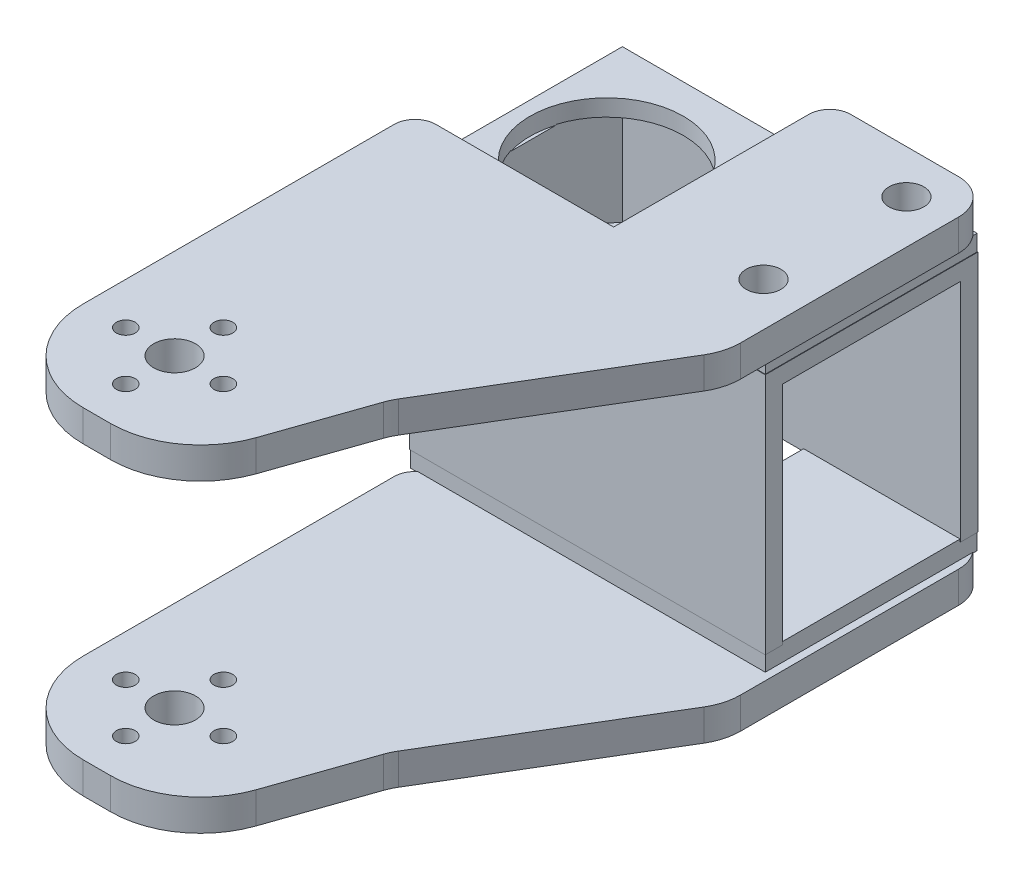
SolidWorks part; units mm, degrees
ref_plane "Front Plane" through (0, 0, 0) normal (0, 0, 1) x (1, 0, 0)
ref_plane "Top Plane" through (0, 0, 0) normal (0, 1, 0) x (1, 0, 0)
ref_plane "Right Plane" through (0, 0, 0) normal (1, 0, 0) x (0, 0, -1)
ref_plane "PY_m23_125" through (0, -23.125, 0) normal (0, 1, 0) x (1, 0, 0)
sketch "S_prism1" plane through (0, -23.125, 0) normal (0, 1, 0) x (1, 0, 0)
  line L0 (-0.1, -13) -> (3.8289, -13)
  line L1 (16.0129, -4.3379) -> (20.7288, 9.2202)
  line L2 (21.4248, 10.708) -> (37.8599, 38.0999)
  line L3 (39, 42.2159) -> (39, 73.5)
  line L4 (34, 78.5) -> (18.5, 78.5)
  line L5 (15.5, 75.5) -> (15.5, 47.5)
  line L6 (15.5, 47.5) -> (-10, 47.5)
  line L7 (-13, 44.5) -> (-13, -0.1)
  arc A0 (-13, -0.1) -> (-0.1, -13) centre (-0.1001, -0.1001) ccw
  arc A1 (3.8289, -13) -> (16.0129, -4.3379) centre (3.8289, -0.1) ccw
  arc A2 (20.7288, 9.2202) -> (21.4248, 10.708) centre (28.2833, 6.5929) cw
  arc A3 (37.8599, 38.0999) -> (39, 42.2159) centre (31, 42.2159) ccw
  arc A4 (39, 73.5) -> (34, 78.5) centre (33.9999, 73.4999) ccw
  arc A5 (18.5, 78.5) -> (15.5, 75.5) centre (18.5001, 75.4999) ccw
  arc A6 (-10, 47.5) -> (-13, 44.5) centre (-9.9999, 44.4999) ccw
extrude "Boss_1" add sketch "S_prism1" along normal blind 4.5
ref_plane "PY_p18_625" through (0, 18.625, 0) normal (0, 1, 0) x (1, 0, 0)
sketch "S_cyl2" plane through (0, 18.625, 0) normal (0, 1, 0) x (1, 0, 0)
  circle A0 centre (0, 0) radius 9
  dimension "D1_S_cyl2" = 18
extrude "Boss_2" add sketch "S_cyl2" along normal blind 2
ref_plane "PY_p20_625" through (0, 20.625, 0) normal (0, 1, 0) x (1, 0, 0)
sketch "S_prism3" plane through (0, 20.625, 0) normal (0, 1, 0) x (1, 0, 0)
  line L0 (-0.1, -13) -> (3.8289, -13)
  line L1 (16.0129, -4.3379) -> (20.7288, 9.2202)
  line L2 (21.4248, 10.708) -> (37.8599, 38.0999)
  line L3 (39, 42.2159) -> (39, 73.5)
  line L4 (34, 78.5) -> (18.5, 78.5)
  line L5 (15.5, 75.5) -> (15.5, 47.5)
  line L6 (15.5, 47.5) -> (-10, 47.5)
  line L7 (-13, 44.5) -> (-13, -0.1)
  arc A0 (-13, -0.1) -> (-0.1, -13) centre (-0.1001, -0.1001) ccw
  arc A1 (3.8289, -13) -> (16.0129, -4.3379) centre (3.8289, -0.1) ccw
  arc A2 (20.7288, 9.2202) -> (21.4248, 10.708) centre (28.2833, 6.5929) cw
  arc A3 (37.8599, 38.0999) -> (39, 42.2159) centre (31, 42.2159) ccw
  arc A4 (39, 73.5) -> (34, 78.5) centre (33.9999, 73.4999) ccw
  arc A5 (18.5, 78.5) -> (15.5, 75.5) centre (18.5001, 75.4999) ccw
  arc A6 (-10, 47.5) -> (-13, 44.5) centre (-9.9999, 44.4999) ccw
extrude "Boss_3" add sketch "S_prism3" along normal blind 4.5
ref_plane "PZ_m77_260" through (0, 0, -77.26) normal (0, 0, 1) x (1, 0, 0)
sketch "S_box4" plane through (0, 0, -77.26) normal (0, 0, 1) x (1, 0, 0)
  line L0 (-13.01, -16.4) -> (-10.51, -16.4)
  line L1 (-10.51, -16.4) -> (-10.51, 18.4)
  line L2 (-10.51, 18.4) -> (-13.01, 18.4)
  line L3 (-13.01, 18.4) -> (-13.01, -16.4)
  dimension "P1" = 13.01
  dimension "P2" = 16.4
  dimension "P3" = 10.51
  dimension "P4" = 16.4
  dimension "P5" = 10.51
  dimension "P6" = 18.4
  dimension "P7" = 13.01
  dimension "P8" = 18.4
extrude "Boss_4" add sketch "S_box4" along normal blind 30.52
sketch "S_box5" plane through (0, 0, -77.26) normal (0, 0, 1) x (1, 0, 0)
  line L0 (-13.01, -16.4) -> (38.01, -16.4)
  line L1 (38.01, -16.4) -> (38.01, 18.4)
  line L2 (38.01, 18.4) -> (-13.01, 18.4)
  line L3 (-13.01, 18.4) -> (-13.01, -16.4)
  dimension "P1" = 13.01
  dimension "P2" = 16.4
  dimension "P3" = 38.01
  dimension "P4" = 16.4
  dimension "P5" = 38.01
  dimension "P6" = 18.4
  dimension "P7" = 13.01
  dimension "P8" = 18.4
extrude "Boss_5" add sketch "S_box5" along normal blind 2.5
ref_plane "PZ_m49_240" through (0, 0, -49.24) normal (0, 0, 1) x (1, 0, 0)
sketch "S_box6" plane through (0, 0, -49.24) normal (0, 0, 1) x (1, 0, 0)
  line L0 (-13.01, -16.4) -> (38.01, -16.4)
  line L1 (38.01, -16.4) -> (38.01, 18.4)
  line L2 (38.01, 18.4) -> (-13.01, 18.4)
  line L3 (-13.01, 18.4) -> (-13.01, -16.4)
  dimension "P1" = 13.01
  dimension "P2" = 16.4
  dimension "P3" = 38.01
  dimension "P4" = 16.4
  dimension "P5" = 38.01
  dimension "P6" = 18.4
  dimension "P7" = 13.01
  dimension "P8" = 18.4
extrude "Boss_6" add sketch "S_box6" along normal blind 2.5
sketch "S_box7" plane through (0, 0, -77.26) normal (0, 0, 1) x (1, 0, 0)
  line L0 (-13.01, 16) -> (38.01, 16)
  line L1 (38.01, 16) -> (38.01, 18.4)
  line L2 (38.01, 18.4) -> (-13.01, 18.4)
  line L3 (-13.01, 18.4) -> (-13.01, 16)
  dimension "P1" = 13.01
  dimension "P2" = 16
  dimension "P3" = 38.01
  dimension "P4" = 16
  dimension "P5" = 38.01
  dimension "P6" = 18.4
  dimension "P7" = 13.01
  dimension "P8" = 18.4
extrude "Boss_7" add sketch "S_box7" along normal blind 30.52
ref_plane "PZ_m77_190" through (0, 0, -77.19) normal (0, 0, 1) x (1, 0, 0)
sketch "S_box8" plane through (0, 0, -77.19) normal (0, 0, 1) x (1, 0, 0)
  line L0 (15.5, -18.725) -> (37.94, -18.725)
  line L1 (37.94, -18.725) -> (37.94, -16.05)
  line L2 (37.94, -16.05) -> (15.5, -16.05)
  line L3 (15.5, -16.05) -> (15.5, -18.725)
  dimension "P1" = 15.5
  dimension "P2" = 18.725
  dimension "P3" = 37.94
  dimension "P4" = 18.725
  dimension "P5" = 37.94
  dimension "P6" = 16.05
  dimension "P7" = 15.5
  dimension "P8" = 16.05
extrude "Boss_8" add sketch "S_box8" along normal blind 30.38
ref_plane "PZ_m48_500" through (0, 0, -48.5) normal (0, 0, 1) x (1, 0, 0)
sketch "S_box9" plane through (0, 0, -48.5) normal (0, 0, 1) x (1, 0, 0)
  line L0 (-12.94, -18.725) -> (15.53, -18.725)
  line L1 (15.53, -18.725) -> (15.53, -16.05)
  line L2 (15.53, -16.05) -> (-12.94, -16.05)
  line L3 (-12.94, -16.05) -> (-12.94, -18.725)
  dimension "P1" = 12.94
  dimension "P2" = 18.725
  dimension "P3" = 15.53
  dimension "P4" = 18.725
  dimension "P5" = 15.53
  dimension "P6" = 16.05
  dimension "P7" = 12.94
  dimension "P8" = 16.05
extrude "Boss_9" add sketch "S_box9" along normal blind 1.69
sketch "S_box10" plane through (0, 0, -77.19) normal (0, 0, 1) x (1, 0, 0)
  line L0 (15.5, 18.3) -> (37.94, 18.3)
  line L1 (37.94, 18.3) -> (37.94, 20.725)
  line L2 (37.94, 20.725) -> (15.5, 20.725)
  line L3 (15.5, 20.725) -> (15.5, 18.3)
  dimension "P1" = 15.5
  dimension "P2" = 18.3
  dimension "P3" = 37.94
  dimension "P4" = 18.3
  dimension "P5" = 37.94
  dimension "P6" = 20.725
  dimension "P7" = 15.5
  dimension "P8" = 20.725
extrude "Boss_10" add sketch "S_box10" along normal blind 30.38
sketch "S_box11" plane through (0, 0, -48.5) normal (0, 0, 1) x (1, 0, 0)
  line L0 (-12.94, 18.3) -> (15.53, 18.3)
  line L1 (15.53, 18.3) -> (15.53, 20.725)
  line L2 (15.53, 20.725) -> (-12.94, 20.725)
  line L3 (-12.94, 20.725) -> (-12.94, 18.3)
  dimension "P1" = 12.94
  dimension "P2" = 18.3
  dimension "P3" = 15.53
  dimension "P4" = 18.3
  dimension "P5" = 15.53
  dimension "P6" = 20.725
  dimension "P7" = 12.94
  dimension "P8" = 20.725
extrude "Boss_11" add sketch "S_box11" along normal blind 1.69
ref_plane "PY_m23_225" through (0, -23.225, 0) normal (0, 1, 0) x (1, 0, 0)
sketch "S_hole12" plane through (0, -23.225, 0) normal (0, 1, 0) x (1, 0, 0)
  circle A0 centre (0, 0) radius 3
  dimension "D1_S_hole12" = 6
extrude "Hole_12" cut sketch "S_hole12" along normal blind 4.7
sketch "S_hole13" plane through (0, -23.225, 0) normal (0, 1, 0) x (1, 0, 0)
  circle A0 centre (7, 0) radius 1.35
  dimension "D1_S_hole13" = 2.7
  dimension "P2" = 7
extrude "Hole_13" cut sketch "S_hole13" along normal blind 4.7
sketch "S_hole14" plane through (0, -23.225, 0) normal (0, 1, 0) x (1, 0, 0)
  circle A0 centre (0, -7) radius 1.35
  dimension "D1_S_hole14" = 2.7
  dimension "P2" = 7
extrude "Hole_14" cut sketch "S_hole14" along normal blind 4.7
sketch "S_hole15" plane through (0, -23.225, 0) normal (0, 1, 0) x (1, 0, 0)
  circle A0 centre (-7, 0) radius 1.35
  dimension "D1_S_hole15" = 2.7
  dimension "P2" = 7
extrude "Hole_15" cut sketch "S_hole15" along normal blind 4.7
sketch "S_hole16" plane through (0, -23.225, 0) normal (0, 1, 0) x (1, 0, 0)
  circle A0 centre (0, 7) radius 1.35
  dimension "D1_S_hole16" = 2.7
  dimension "P2" = 7
extrude "Hole_16" cut sketch "S_hole16" along normal blind 4.7
ref_plane "PY_p18_525" through (0, 18.525, 0) normal (0, 1, 0) x (1, 0, 0)
sketch "S_hole17" plane through (0, 18.525, 0) normal (0, 1, 0) x (1, 0, 0)
  circle A0 centre (0, 0) radius 3
  dimension "D1_S_hole17" = 6
extrude "Hole_17" cut sketch "S_hole17" along normal blind 6.7
sketch "S_hole18" plane through (0, 18.525, 0) normal (0, 1, 0) x (1, 0, 0)
  circle A0 centre (7, 0) radius 1.35
  dimension "D1_S_hole18" = 2.7
  dimension "P2" = 7
extrude "Hole_18" cut sketch "S_hole18" along normal blind 6.7
sketch "S_hole19" plane through (0, 18.525, 0) normal (0, 1, 0) x (1, 0, 0)
  circle A0 centre (0, -7) radius 1.35
  dimension "D1_S_hole19" = 2.7
  dimension "P2" = 7
extrude "Hole_19" cut sketch "S_hole19" along normal blind 6.7
sketch "S_hole20" plane through (0, 18.525, 0) normal (0, 1, 0) x (1, 0, 0)
  circle A0 centre (-7, 0) radius 1.35
  dimension "D1_S_hole20" = 2.7
  dimension "P2" = 7
extrude "Hole_20" cut sketch "S_hole20" along normal blind 6.7
sketch "S_hole21" plane through (0, 18.525, 0) normal (0, 1, 0) x (1, 0, 0)
  circle A0 centre (0, 7) radius 1.35
  dimension "D1_S_hole21" = 2.7
  dimension "P2" = 7
extrude "Hole_21" cut sketch "S_hole21" along normal blind 6.7
ref_plane "PY_p15_900" through (0, 15.9, 0) normal (0, 1, 0) x (1, 0, 0)
sketch "S_hole22" plane through (0, 15.9, 0) normal (0, 1, 0) x (1, 0, 0)
  circle A0 centre (0, 62) radius 11
  dimension "D1_S_hole22" = 22
  dimension "P2" = 62
extrude "Hole_22" cut sketch "S_hole22" along normal blind 2.6
sketch "S_hole23" plane through (0, 15.9, 0) normal (0, 1, 0) x (1, 0, 0)
  circle A0 centre (8.3, 51.75) radius 1.1
  dimension "D1_S_hole23" = 2.2
  dimension "P2" = 8.3
  dimension "P3" = 51.75
extrude "Hole_23" cut sketch "S_hole23" along normal blind 2.6
sketch "S_hole24" plane through (0, 15.9, 0) normal (0, 1, 0) x (1, 0, 0)
  circle A0 centre (32.75, 72.25) radius 1.1
  dimension "D1_S_hole24" = 2.2
  dimension "P2" = 32.75
  dimension "P3" = 72.25
extrude "Hole_24" cut sketch "S_hole24" along normal blind 2.6
sketch "S_hole25" plane through (0, 15.9, 0) normal (0, 1, 0) x (1, 0, 0)
  circle A0 centre (32.75, 51.75) radius 1.1
  dimension "D1_S_hole25" = 2.2
  dimension "P2" = 32.75
  dimension "P3" = 51.75
extrude "Hole_25" cut sketch "S_hole25" along normal blind 2.6
ref_plane "PY_p18_450" through (0, 18.45, 0) normal (0, 1, 0) x (1, 0, 0)
sketch "S_hole26" plane through (0, 18.45, 0) normal (0, 1, 0) x (1, 0, 0)
  circle A0 centre (32.75, 72.25) radius 2.5
  dimension "D1_S_hole26" = 5
  dimension "P2" = 32.75
  dimension "P3" = 72.25
extrude "Hole_26" cut sketch "S_hole26" along normal blind 6.775
sketch "S_hole27" plane through (0, 18.45, 0) normal (0, 1, 0) x (1, 0, 0)
  circle A0 centre (32.75, 51.75) radius 2.5
  dimension "D1_S_hole27" = 5
  dimension "P2" = 32.75
  dimension "P3" = 51.75
extrude "Hole_27" cut sketch "S_hole27" along normal blind 6.775
equation "\"plate_t\" = 3"
equation "\"clearance\" = 0.4"
